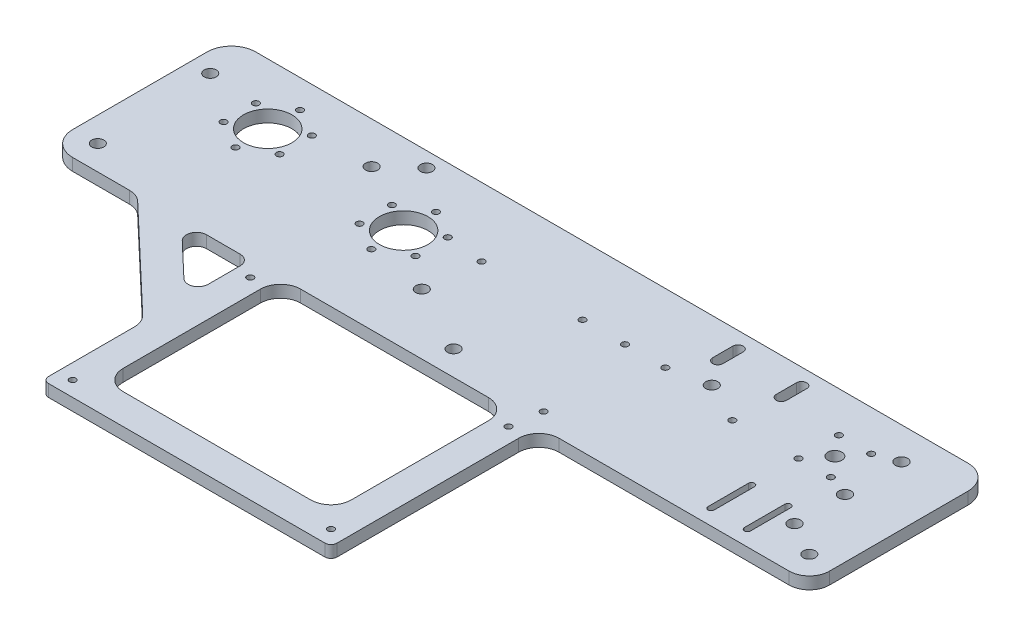
SolidWorks part; units mm, degrees
material "Policarbonato"
ref_plane "Plano frontal" through (0, 0, 0) normal (0, 0, 1) x (1, 0, 0)
ref_plane "Plano superior" through (0, 0, 0) normal (0, 1, 0) x (1, 0, 0)
ref_plane "Plano direito" through (0, 0, 0) normal (1, 0, 0) x (0, 0, -1)
sketch "Esboço1" plane through (0, 0, 0) normal (0, 1, 0) x (1, 0, 0)
  line L3 (-85.5279, -153.6487) -> (51.4721, -153.6487)
  line L4 (54.4721, -150.6487) -> (54.4721, -60.6487)
  line L6 (188.5279, -40.6487) -> (188.5279, 28)
  line L7 (176.5279, 40) -> (-176.5279, 40)
  line L8 (-188.5279, 28) -> (-188.5279, -38.6487)
  line L9 (-176.5279, -50.6487) -> (-148.4656, -50.6487)
  line L10 (-141.5771, -53.3996) -> (-91.6394, -100.8535)
  line L11 (-88.5279, -108.1025) -> (-88.5279, -150.6487)
  line L12 (-110.1764, -50.6487) -> (-93.5279, -50.6487)
  line L13 (-88.5279, -55.6487) -> (-88.5279, -71.4691)
  line L14 (-96.9722, -75.0936) -> (-113.6207, -59.2732)
  line L15 (39.4721, -60.6487) -> (39.4721, -128.6487)
  line L16 (29.4721, -138.6487) -> (-63.5279, -138.6487)
  line L17 (-73.5279, -128.6487) -> (-73.5279, -60.6487)
  line L18 (-63.5279, -50.6487) -> (29.4721, -50.6487)
  line L20 (132.5279, 0) -> (148.5279, 0) construction
  line L21 (132.5279, 0) -> (132.5279, 20) construction
  line L22 (132.5279, 20) -> (148.5279, 20) construction
  line L23 (148.5279, 0) -> (148.5279, 20) construction
  line L24 (132.5279, 0) -> (148.5279, 20) construction
  line L25 (132.5279, 20) -> (148.5279, 0) construction
  line L30 (64.4721, -50.6487) -> (178.5279, -50.6487)
  line L31 (150.2221, -43) -> (150.2221, -23) construction
  line L32 (148.7221, -43) -> (148.7221, -23)
  line L33 (151.7221, -43) -> (151.7221, -23)
  line L34 (141.2221, -45.2211) -> (141.2221, -21.4375) construction
  line L36 (132.2221, -43) -> (132.2221, -23) construction
  line L37 (133.7221, -43) -> (133.7221, -23)
  line L38 (130.7221, -43) -> (130.7221, -23)
  line L39 (49.2221, -43) -> (150.2221, -43) construction
  line L40 (54.4721, -120.5) -> (144.9721, -120.5) construction
  line L41 (54.4721, -120.5) -> (54.4721, -7) construction
  line L42 (54.4721, -7) -> (144.9721, -7) construction
  line L43 (144.9721, -120.5) -> (144.9721, -7) construction
  line L44 (54.4721, -120.5) -> (144.9721, -7) construction
  line L45 (54.4721, -7) -> (144.9721, -120.5) construction
  line L46 (70.5279, 22) -> (70.5279, 32) construction
  line L47 (67.9779, 22) -> (67.9779, 32)
  line L48 (73.0779, 22) -> (73.0779, 32)
  line L49 (102.0279, 22) -> (102.0279, 32) construction
  line L50 (99.4779, 22) -> (99.4779, 32)
  line L51 (104.5779, 22) -> (104.5779, 32)
  circle A0 centre (-81.0279, -58.1487) radius 1.6
  circle A1 centre (-81.0279, -146.1487) radius 1.6
  circle A2 centre (46.9721, -58.1487) radius 1.6
  circle A3 centre (46.9721, -146.1487) radius 1.6
  circle A8 centre (176.311, -38.4318) radius 3
  circle A9 centre (0, -38.4318) radius 3
  circle A11 centre (-140.5279, 10) radius 12
  circle A20 centre (-140.5279, 10) radius 16 construction
  circle A21 centre (-140.5279, -6) radius 1.6
  circle A22 centre (-154.3843, 2) radius 1.6
  circle A23 centre (-154.3843, 18) radius 1.6
  circle A24 centre (-84.3674, 32.5) radius 3
  circle A25 centre (-176.311, -38.4318) radius 3
  circle A26 centre (140.5279, 10) radius 3.5
  circle A27 centre (148.5279, 0) radius 1.6
  circle A28 centre (148.5279, 20) radius 1.6
  circle A29 centre (132.5279, 0) radius 1.6
  circle A30 centre (132.5279, 20) radius 1.6
  arc A31 (51.4721, -153.6487) -> (54.4721, -150.6487) centre (51.4721, -150.6487) ccw
  arc A34 (188.5279, 28) -> (176.5279, 40) centre (176.5279, 28) ccw
  arc A35 (-176.5279, 40) -> (-188.5279, 28) centre (-176.5279, 28) ccw
  arc A36 (-188.5279, -38.6487) -> (-176.5279, -50.6487) centre (-176.5279, -38.6487) ccw
  arc A37 (-91.6394, -100.8535) -> (-88.5279, -108.1025) centre (-98.5279, -108.1025) cw
  arc A38 (-88.5279, -150.6487) -> (-85.5279, -153.6487) centre (-85.5279, -150.6487) ccw
  arc A39 (-93.5279, -50.6487) -> (-88.5279, -55.6487) centre (-93.5279, -55.6487) cw
  arc A40 (-88.5279, -71.4691) -> (-96.9722, -75.0936) centre (-93.5279, -71.4691) cw
  arc A41 (-113.6207, -59.2732) -> (-110.1764, -50.6487) centre (-110.1764, -55.6487) cw
  arc A42 (39.4721, -128.6487) -> (29.4721, -138.6487) centre (29.4721, -128.6487) cw
  arc A43 (-63.5279, -138.6487) -> (-73.5279, -128.6487) centre (-63.5279, -128.6487) cw
  arc A44 (-73.5279, -60.6487) -> (-63.5279, -50.6487) centre (-63.5279, -60.6487) cw
  arc A45 (29.4721, -50.6487) -> (39.4721, -60.6487) centre (29.4721, -60.6487) cw
  circle A46 centre (-140.5279, 26) radius 1.6
  circle A47 centre (-126.6715, 18) radius 1.6
  circle A48 centre (-126.6715, 2) radius 1.6
  circle A49 centre (-63.1716, 0) radius 16 construction
  circle A50 centre (-63.1716, -16) radius 1.6
  circle A51 centre (-77.028, -8) radius 1.6
  circle A52 centre (-77.028, 8) radius 1.6
  circle A53 centre (-63.1716, 16) radius 1.6
  circle A54 centre (-49.3152, 8) radius 1.6
  circle A55 centre (-49.3152, -8) radius 1.6
  circle A56 centre (-63.1716, 0) radius 12
  circle A57 centre (-33.5279, -20.6487) radius 3
  circle A58 centre (79.5279, 10) radius 3
  arc A61 (-148.4656, -50.6487) -> (-141.5771, -53.3996) centre (-148.4656, -60.6487) cw
  arc A62 (188.5279, -40.6487) -> (178.5279, -50.6487) centre (178.5279, -40.6487) cw
  arc A63 (54.4721, -60.6487) -> (64.4721, -50.6487) centre (64.4721, -60.6487) cw
  arc A64 (148.7221, -43) -> (151.7221, -43) centre (150.2221, -43) ccw
  arc A65 (151.7221, -23) -> (148.7221, -23) centre (150.2221, -23) ccw
  arc A66 (133.7221, -43) -> (130.7221, -43) centre (132.2221, -43) cw
  arc A67 (130.7221, -23) -> (133.7221, -23) centre (132.2221, -23) cw
  circle A68 centre (99.7221, 0) radius 1.6
  circle A69 centre (49.2221, -43) radius 1.6
  circle A70 centre (150.2221, -43) radius 1.6 construction
  circle A71 centre (-30.5279, 6) radius 1.6
  circle A72 centre (19.4721, 6) radius 1.6
  circle A73 centre (60.5279, 6) radius 1.6
  circle A75 centre (40.5279, 6) radius 1.6
  circle A76 centre (70.5279, 27) radius 2.55 construction
  circle A77 centre (102.0279, 27) radius 2.55 construction
  circle A78 centre (159.4679, 24.07) radius 3.05
  circle A79 centre (159.4679, -3.93) radius 3.05
  circle A80 centre (159.4679, -28.93) radius 3.05
  arc A81 (67.9779, 22) -> (73.0779, 22) centre (70.5279, 22) ccw
  arc A82 (73.0779, 32) -> (67.9779, 32) centre (70.5279, 32) ccw
  arc A83 (99.4779, 22) -> (104.5779, 22) centre (102.0279, 22) ccw
  arc A84 (104.5779, 32) -> (99.4779, 32) centre (102.0279, 32) ccw
  circle A85 centre (-178.5279, 19.5) radius 3
  circle A86 centre (-98.5279, 19.5) radius 3
  point P14 (150.2221, -33)
  point P43 (-140.5279, 10)
  point P70 (-144.4721, -50.6487)
  point P116 (-63.1716, 0)
  point P123 (0, 40)
  point P124 (132.2221, -33)
  point P129 (99.7221, -63.75)
  point P135 (99.7221, -7)
  point P141 (99.7221, -43)
  point P161 (70.5279, 27)
  point P168 (102.0279, 27)
  dimension "D2" = 3
  dimension "D7" = 10
  dimension "D8" = 12
  dimension "D10" = 90.6487
  dimension "D11" = 61
  dimension "D12" = 203.9448
  dimension "D13" = 7.5
  dimension "D14" = 104.1605
  dimension "D16" = 12
  dimension "D20" = 10
  dimension "D21" = 3
  dimension "D22" = 48.4318
  dimension "D23" = 32
  dimension "D24" = 3.2
  dimension "D25" = 6
  dimension "D26" = 24
  dimension "D27" = 48
  dimension "D28" = 30
  dimension "D29" = 40
  dimension "D30" = 6
  dimension "D34" = 30
  dimension "D31" = 32
  dimension "D32" = 3.2
  dimension "D33" = 24
  dimension "D35" = 6
  dimension "D36" = 155
  dimension "D37" = 30
  dimension "D44" = 7
  dimension "D48" = 10
  dimension "D54" = 143
  dimension "D6" = 10
  dimension "D58" = 5
  dimension "D62" = 1.5
  dimension "D68" = 101
  dimension "D72" = 80
  dimension "D75" = 5.1
  dimension "D80" = 14.07
  dimension "D82" = 6.1
  dimension "D83" = 10
  dimension "D1" = 137
  dimension "D9" = 377.0558
  dimension "D15" = 66.6487
  dimension "D17" = 32.0558
  dimension "D18" = 100
  dimension "D19" = 42.5462
  dimension "D38" = 48
  dimension "D39" = 15
  dimension "D40" = 12.2169
  dimension "D41" = 12.2169
  dimension "D42" = 16
  dimension "D43" = 20
  dimension "D45" = 15
  dimension "D46" = 15
  dimension "D47" = 15
  dimension "D49" = 7.5
  dimension "D50" = 7.5
  dimension "D51" = 88
  dimension "D52" = 128
  dimension "D53" = 93
  dimension "D55" = 15
  dimension "D56" = 20.6487
  dimension "D57" = 68
  dimension "D59" = 10
  dimension "D60" = 20.5
  dimension "D61" = 20
  dimension "D63" = 9
  dimension "D64" = 113.5
  dimension "D65" = 90.5
  dimension "D66" = 7
  dimension "D67" = 43
  dimension "D69" = 34
  dimension "D70" = 110
  dimension "D71" = 50
  dimension "D73" = 20
  dimension "D74" = 31.5
  dimension "D76" = 13
  dimension "D77" = 10
  dimension "D78" = 25
  dimension "D79" = 28
  dimension "D81" = 18.94
  dimension "D84" = 80
extrude "Ressalto-extrusão1" add sketch "Esboço1" against normal blind 6
